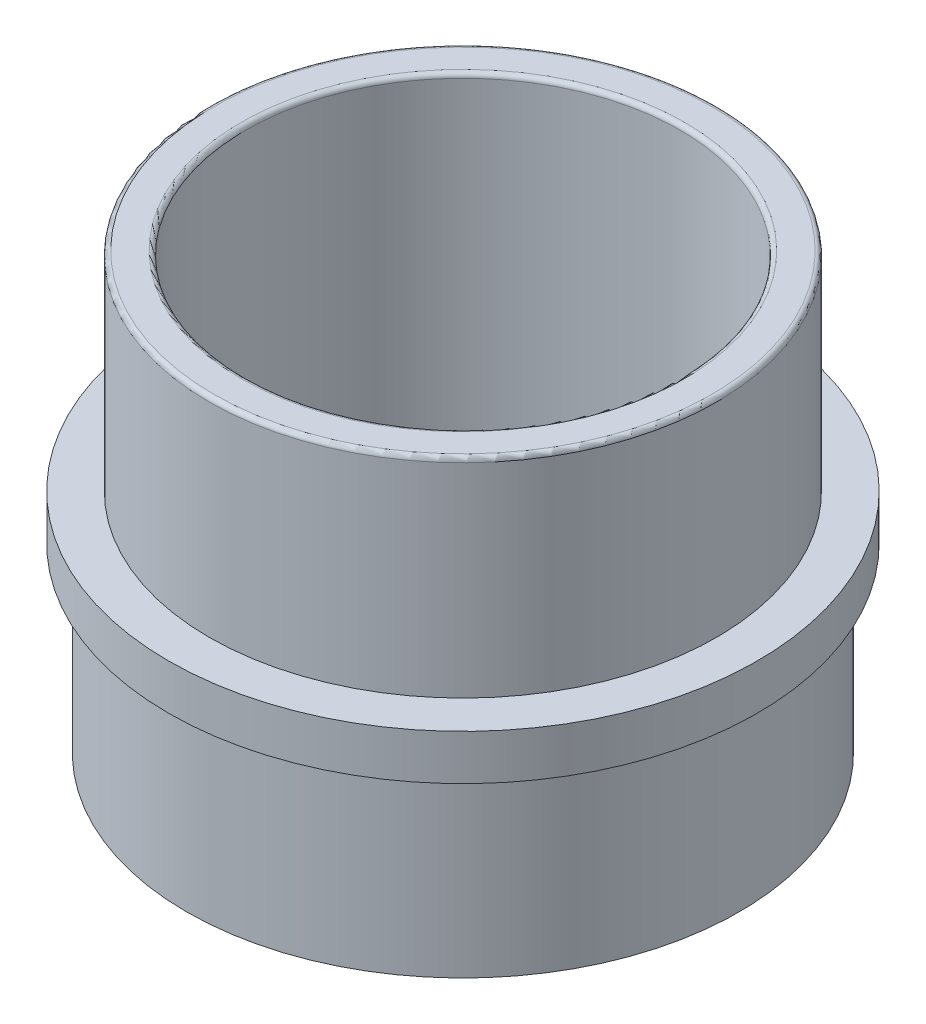
SolidWorks part; units mm, degrees
material "7075-T6 (SN)"
ref_plane "Front Plane" through (0, 0, 0) normal (0, 0, 1) x (1, 0, 0)
ref_plane "Top Plane" through (0, 0, 0) normal (0, 1, 0) x (1, 0, 0)
ref_plane "Right Plane" through (0, 0, 0) normal (1, 0, 0) x (0, 0, -1)
sketch "Sketch1" plane through (0, 0, 0) normal (0, 1, 0) x (1, 0, 0)
  circle A1 centre (0, 0) radius 32.5
extrude "Boss-Extrude1" add sketch "Sketch1" along normal blind 5
sketch "Sketch2" plane through (0, 0, 0) normal (0, -1, 0) x (1, 0, 0)
  circle A0 centre (0, 0) radius 30.5
extrude "Boss-Extrude2" add sketch "Sketch2" along normal blind 15 and the other way up to surface from offset 5 other way up to face at (0, 0, 32.5)
sketch "Sketch3" plane through (0, 0, 0) normal (0, -1, 0) x (-1, 0, 0)
  circle A0 centre (0, 0) radius 24
extrude "Cut-Extrude3" cut sketch "Sketch3" along normal through all draft 12 from offset 10 draft outward yes
fillet "Fillet1" radius 4 1 edges at (0, -20, -26.1256)
sketch "Sketch4" plane through (0, -10, 0) normal (0, -1, 0) x (1, 0, 0)
  circle A0 centre (0, 0) radius 24
extrude "Cut-Extrude4" cut sketch "Sketch4" against normal through all
fillet "Fillet2" radius 12 1 edges at (0, -10, -24)
sketch "Sketch5" plane through (0, 5, 0) normal (0, 1, 0) x (1, 0, 0)
  circle A0 centre (0, 0) radius 28
  circle A1 centre (0, 0) radius 24
extrude "Boss-Extrude3" add sketch "Sketch5" along normal blind 23
fillet "Fillet3" radius 0.5 2 edges at (0, 28, 28) (0, 28, 24)
